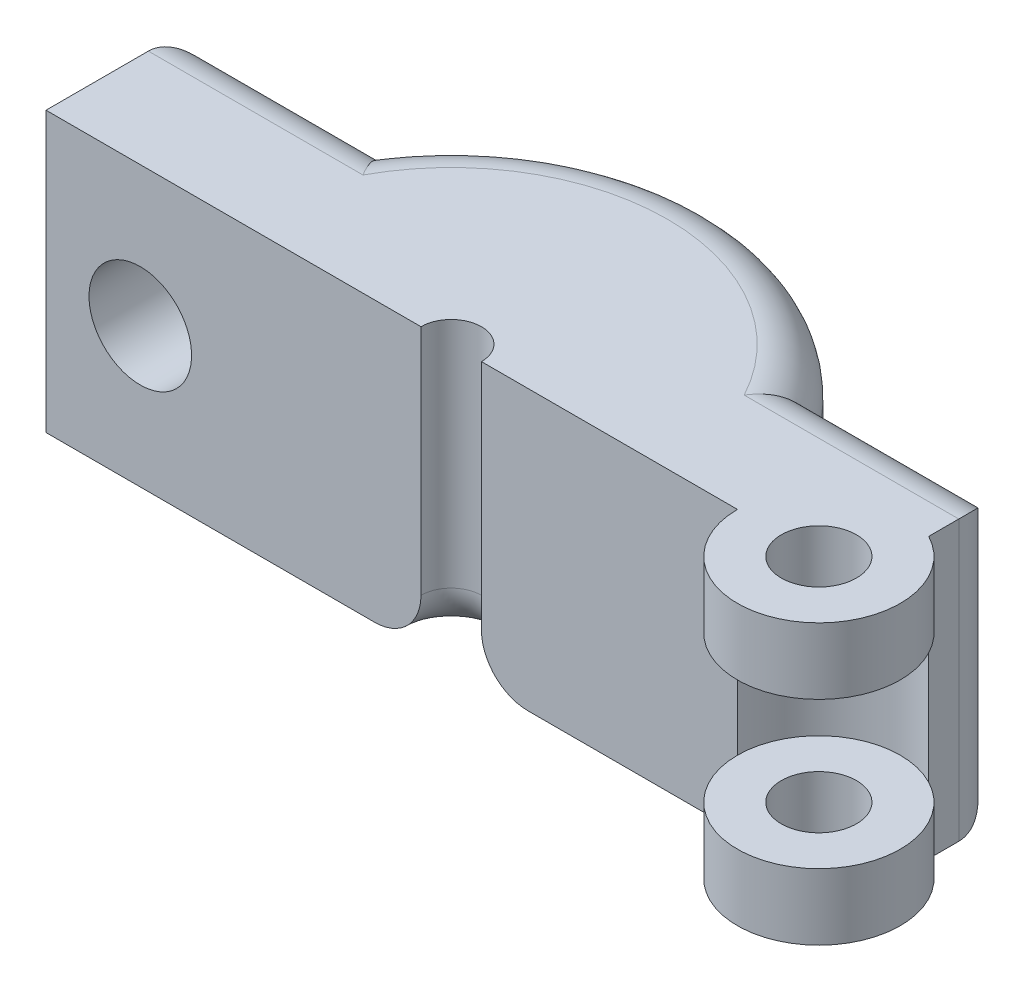
SolidWorks part; units mm, degrees
ref_plane "Front Plane" through (0, 0, 0) normal (0, 0, 1) x (1, 0, 0)
ref_plane "Top Plane" through (0, 0, 0) normal (0, 1, 0) x (1, 0, 0)
ref_plane "Right Plane" through (0, 0, 0) normal (1, 0, 0) x (0, 0, -1)
sketch "Sketch1" plane through (0, 0, 0) normal (0, 1, 0) x (1, 0, 0)
  line L0 (-22.12, 0) -> (-1.651, 0)
  line L2 (0, 0) -> (0, 14.351) construction
  line L3 (-11.8274, 8.128) -> (-22.12, 8.128)
  line L6 (-22.12, 8.128) -> (-22.12, 0)
  line L7 (15.625, 0) -> (1.651, 0)
  line L8 (11.8274, 8.128) -> (22.12, 8.128)
  line L9 (22.12, 8.128) -> (22.12, 3.944)
  line L10 (20.07, 0) -> (22.12, 0) construction
  arc A0 (1.651, 0) -> (-1.651, 0) centre (0, 0) ccw
  arc A1 (11.8274, 8.128) -> (-11.8274, 8.128) centre (0, 0) ccw
  arc A3 (15.625, 0) -> (22.12, 3.944) centre (20.07, 0) ccw
  circle A4 centre (20.07, 0) radius 2.05
  dimension "D1" = 3.302
  dimension "D2" = 12.7
  dimension "D5" = 4.445
  dimension "4.1mm" = 4.1
  dimension "D3" = 20.07
  dimension "D4" = 8.128
extrude "Boss-Extrude1" add sketch "Sketch1" along normal blind 15.24
ref_plane "Plane1" through (0, 7.62, 0) normal (0, 1, 0) x (1, 0, 0)
sketch "Sketch2" plane through (0, 7.62, 0) normal (0, 1, 0) x (1, 0, 0)
  circle A0 centre (20.07, 0) radius 4.445
  arc A1 (15.625, 0) -> (22.12, 3.944) centre (20.07, 0) ccw construction
extrude "Cut-Extrude1" cut sketch "Sketch2" against normal mid plane 8.001
sketch "Sketch3" plane through (0, 0, -8.128) normal (0, 0, -1) x (-1, 0, 0)
  line L0 (11.8274, 7.62) -> (22.12, 7.62) construction
  line L1 (11.8274, 15.24) -> (11.8274, 0) construction
  line L2 (22.12, 15.24) -> (22.12, 0) construction
  circle A0 centre (16.9737, 7.62) radius 2.8
  dimension "D1" = 5.6
extrude "Cut-Extrude2" cut sketch "Sketch3" against normal up to surface (8.128 mm away) up to face at (-11.8855, 7.62, 0)
fillet "Fillet1" radius 2.54 8 edges at (0, 0, -14.351) (16.9737, 0, -8.128) (-16.9737, 0, -8.128) (-16.9737, 15.24, -8.128) (16.9737, 15.24, -8.128) (0, 15.24, -14.351) (-22.12, 7.62, -8.128) (22.12, 7.62, -8.128)
fillet "Fillet2" radius 2.54 1 edges at (0, 0, -1.651)
